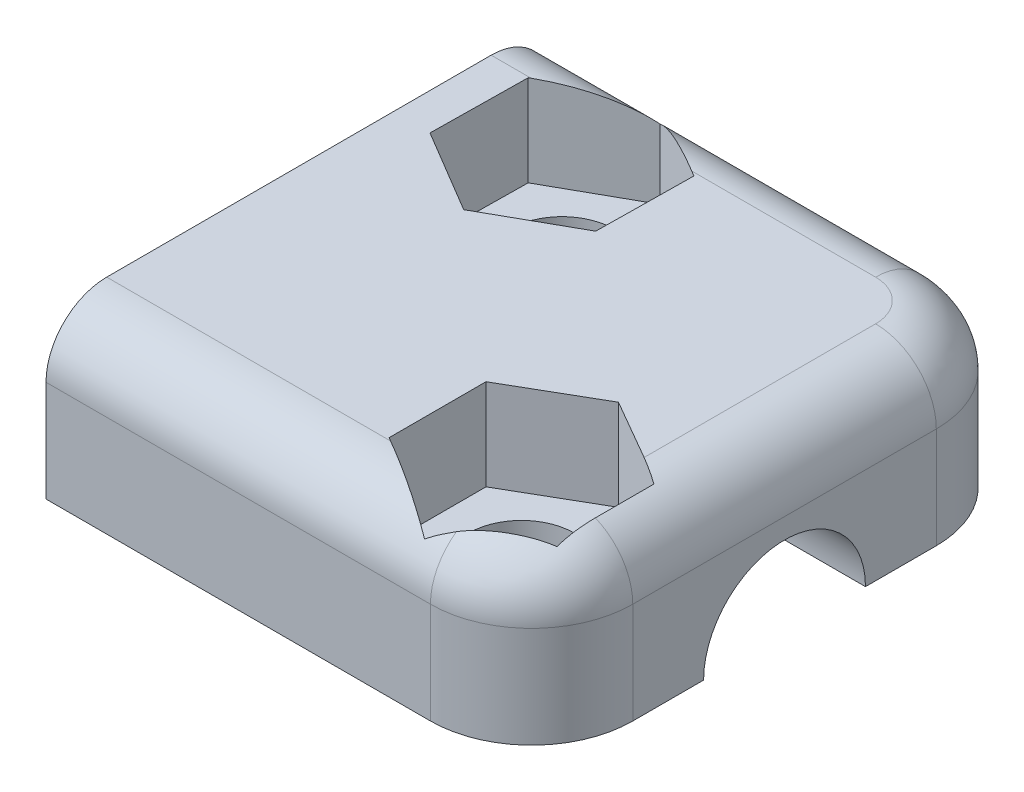
SolidWorks part; units mm, degrees
ref_plane "Front Plane" through (0, 0, 0) normal (0, 0, 1) x (1, 0, 0)
ref_plane "Top Plane" through (0, 0, 0) normal (0, 1, 0) x (1, 0, 0)
ref_plane "Right Plane" through (0, 0, 0) normal (1, 0, 0) x (0, 0, -1)
sketch "Sketch1" plane through (0, 0, 0) normal (0, 1, 0) x (1, 0, 0)
  line L1 (-12, 12.5) -> (12, 12.5)
  line L2 (-12, 12.5) -> (-12, -12.5)
  line L3 (-12, -12.5) -> (12, -12.5)
  line L4 (12, 12.5) -> (12, -12.5)
  line L5 (-12, 12.5) -> (12, -12.5) construction
  line L6 (-12, -12.5) -> (12, 12.5) construction
  point P0 (0, 0)
  dimension "D1" = 25
  dimension "D2" = 24
extrude "Boss-Extrude1" add sketch "Sketch1" along normal blind 8
sketch "Sketch2" plane through (-12, 0, 0) normal (-1, 0, 0) x (0, 0, 1)
  circle A0 centre (0, 0) radius 4
  dimension "D1" = 8
extrude "Cut-Extrude1" cut sketch "Sketch2" against normal through all
sketch "Sketch3" plane through (0, 0, 0) normal (0, -1, 0) x (1, 0, 0)
  line L0 (-6, -7) -> (6, 7) construction
  line L1 (-6, -7) -> (12.0808, -7) construction
  circle A0 centre (-6, -7) radius 2.6
  circle A1 centre (6, 7) radius 2.6
extrude "Cut-Extrude2" cut sketch "Sketch3" against normal through all
fillet "Fillet1" radius 3 3 edges at (0, 8, -12.5) (12, 8, 0) (0, 8, 12.5)
fillet "Fillet2" radius 5 4 edges at (11.1213, 7.1213, -11.6213) (11.1213, 7.1213, 11.6213) (12, 2.5, 12.5) (12, 2.5, -12.5)
sketch "Sketch4" plane through (0, 8, 0) normal (0, 1, 0) x (1, 0, 0)
  line L1 (6, -11.792) -> (10.15, -9.396)
  line L2 (10.15, -9.396) -> (10.15, -4.604)
  line L3 (10.15, -4.604) -> (6, -2.208)
  line L4 (6, -2.208) -> (1.85, -4.604)
  line L5 (1.85, -4.604) -> (1.85, -9.396)
  line L6 (1.85, -9.396) -> (6, -11.792)
  line L7 (-6.0638, 2.2084) -> (-1.8822, 4.549)
  line L8 (-1.8822, 4.549) -> (-1.8185, 9.3406)
  line L9 (-1.8185, 9.3406) -> (-5.9362, 11.7916)
  line L10 (-5.9362, 11.7916) -> (-10.1178, 9.451)
  line L11 (-10.1178, 9.451) -> (-10.1815, 4.6594)
  line L12 (-10.1815, 4.6594) -> (-6.0638, 2.2084)
  circle A0 centre (6, -7) radius 4.15 construction
  circle A1 centre (-6, 7) radius 4.15 construction
  dimension "D1" = 8.3
extrude "Cut-Extrude3" cut sketch "Sketch4" against normal blind 4.5
